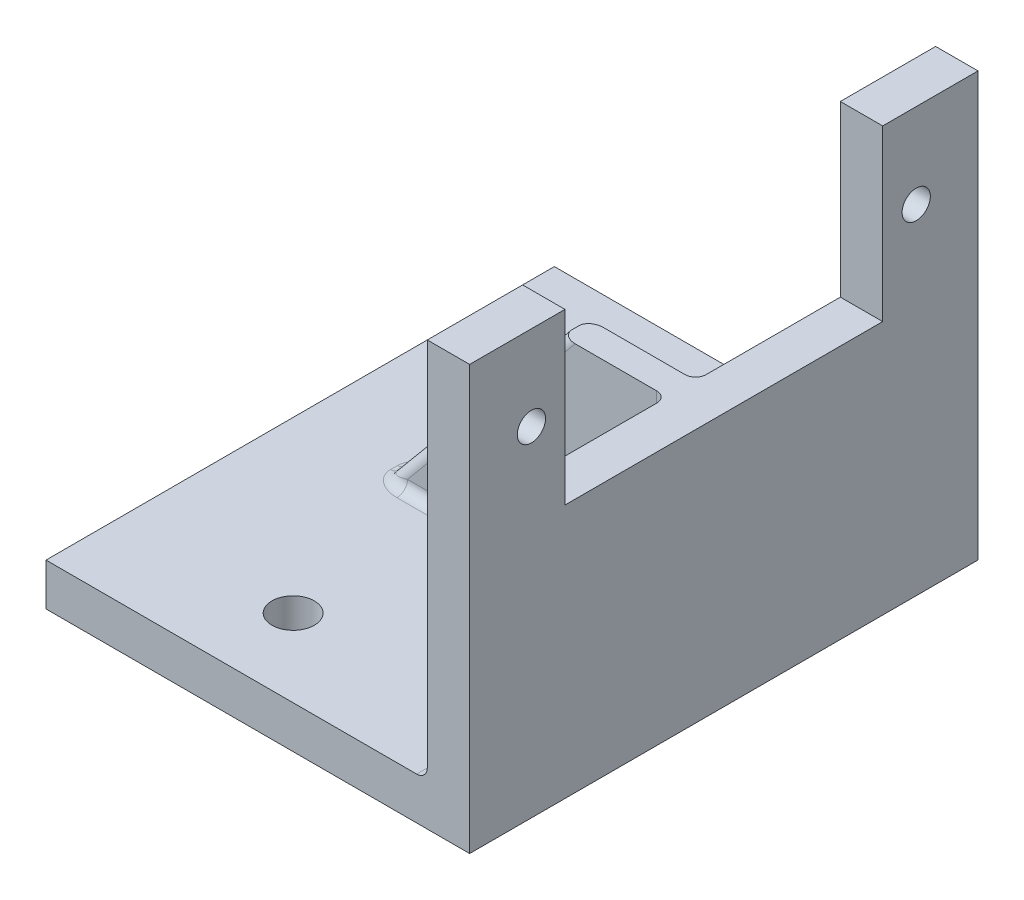
SolidWorks part; units mm, degrees
ref_plane "Front Plane" through (0, 0, 0) normal (0, 0, 1) x (1, 0, 0)
ref_plane "Top Plane" through (0, 0, 0) normal (0, 1, 0) x (1, 0, 0)
ref_plane "Right Plane" through (0, 0, 0) normal (1, 0, 0) x (0, 0, -1)
sketch "Sketch2" plane through (0, 0, 0) normal (0, 0, 1) x (1, 0, 0)
  line L0 (0, 0) -> (-30, 0)
  line L1 (0, 0) -> (0, 30)
  dimension "D1" = 30
extrude "Extrude-Thin1" add sketch "Sketch2" along normal mid plane 36 thin contours L1 L0
sketch "Sketch3" plane through (-3, 0, 0) normal (-1, 0, 0) x (0, 0, 1)
  line L0 (18, 30) -> (-18, 30) construction
  line L1 (-11.25, 30) -> (11.25, 30)
  line L2 (-11.25, 30) -> (-11.25, 18)
  line L3 (-11.25, 18) -> (11.25, 18)
  line L4 (11.25, 30) -> (11.25, 18)
  line L5 (0, 0) -> (0, 30) construction
  line L6 (-18, 24) -> (18, 24) construction
  line L7 (-18, 30) -> (-18, 3) construction
  line L8 (18, 30) -> (18, 3) construction
  circle A0 centre (-13.625, 24) radius 1
  circle A1 centre (13.625, 24) radius 1
  point P9 (0, 18)
  point P16 (-11.25, 24)
  point P21 (0, 0)
  point P22 (-14.4577, 24)
  point P23 (-22.3921, 24)
  dimension "D3" = 2
  dimension "D1" = 22.5
  dimension "D2" = 12
  dimension "D4" = 27.25
extrude "Cut-Extrude1" cut sketch "Sketch3" against normal through all
sketch "Sketch4" plane through (0, 0, 0) normal (0, 0, 1) x (1, 0, 0)
  line L0 (-3, 18) -> (-10.5, 18)
  line L1 (-3, 30) -> (-3, 3) construction
  line L2 (-10.5, 18) -> (-23, 3)
  line L3 (-3, 3) -> (-30, 3) construction
  line L4 (-23, 3) -> (-3, 3)
  line L5 (-3, 3) -> (-3, 18)
  point P4 (0, 0)
  point P10 (-21.7364, 3)
  point P11 (-12.9072, 18)
  point P12 (0, 0)
  dimension "D1" = 20
  dimension "D2" = 7.5
extrude "Boss-Extrude1" add sketch "Sketch4" along normal mid plane 2
fillet "Fillet1" radius 0.75 9 edges at (-16.75, 10.5, -1) (-16.75, 10.5, 1) (-3, 3, 9.5) (-3, 10.5, 1) (-3, 10.5, -1) (-3, 3, -9.5) (-13, 3, -1) (-23, 3, 0) (-13, 3, 1)
sketch "Sketch5" plane through (0, 3, 0) normal (0, 1, 0) x (1, 0, 0)
  line L0 (-18, 12.5) -> (-18, -12.5) construction
  line L1 (-30, -18) -> (-30, 18) construction
  line L3 (-30, 0) -> (-23.3513, 0) construction
  line L4 (-23.3513, -0.25) -> (-23.3513, 0.25) construction
  circle A0 centre (-18, 12.5) radius 1.5
  circle A1 centre (-18, -12.5) radius 1.5
  point P3 (-18, 0)
  point P11 (-25.8752, 12.5)
  dimension "D1" = 3
  dimension "D2" = 25
  dimension "D3" = 12
extrude "Cut-Extrude2" cut sketch "Sketch5" against normal through all
